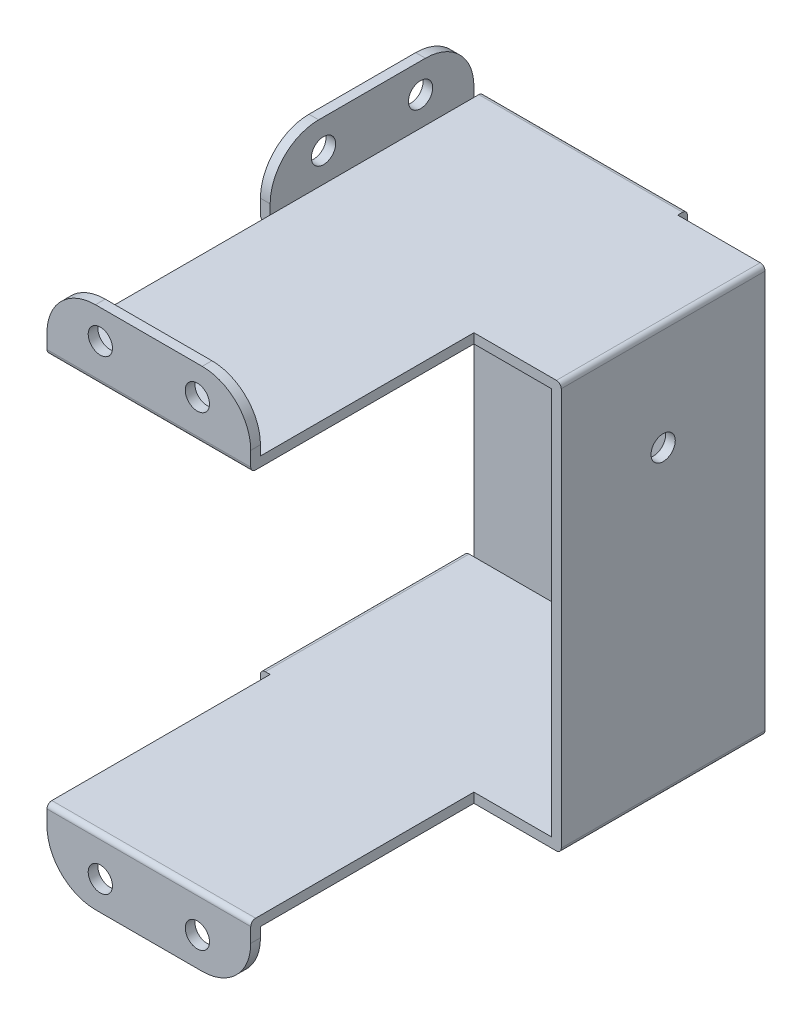
SolidWorks part; units mm, degrees
ref_plane "前视基准面" through (0, 0, 0) normal (0, 0, 1) x (1, 0, 0)
ref_plane "上视基准面" through (0, 0, 0) normal (0, 1, 0) x (1, 0, 0)
ref_plane "右视基准面" through (0, 0, 0) normal (1, 0, 0) x (0, 0, -1)
sketch "草图1" plane through (0, 0, 0) normal (0, 1, 0) x (1, 0, 0)
  line L0 (0, 0) -> (-31, 0)
  line L1 (-31, 0) -> (-31, 21)
  line L2 (-31, 21) -> (0, 21)
  line L3 (0, 21) -> (0, 0)
  dimension "D1" = 21
  dimension "D2" = 31
extrude "凸台-拉伸1" add sketch "草图1" along normal blind 42
shell "抽壳1" thickness 1 removed face at (-15.5, 21, -21) removed face at (-31, 21, -10.5) removed face at (-15.5, 21, 0)
sketch "草图2" plane through (0, 42, 0) normal (0, 1, 0) x (1, 0, 0)
  line L0 (-26, 21) -> (-26, 0)
  line L1 (0, 21) -> (-31, 21) construction
  line L2 (-31, 0) -> (0, 0) construction
  line L3 (-26, 0) -> (-31, 0)
  line L4 (-31, 0) -> (-31, 21)
  line L5 (-31, 21) -> (-26, 21)
  dimension "D1" = 5
extrude "凸台-拉伸2" add sketch "草图2" along normal blind 6
shell "抽壳2" thickness 1 removed face at (-17.8, 26.4, -21) removed face at (-17.8, 26.4, 0) removed face at (-26, 45, -10.5) removed face at (-28.5, 48, -10.5)
sketch "草图3" plane through (0, 0, 0) normal (0, -1, 0) x (1, 0, 0)
  line L0 (-31, 0) -> (-26, 0)
  line L1 (-31, 0) -> (0, 0) construction
  line L2 (-26, 0) -> (-26, -21)
  line L3 (0, -21) -> (-31, -21) construction
  line L4 (-26, -21) -> (-31, -21)
  line L5 (-31, -21) -> (-31, 0)
  dimension "D1" = 5
extrude "凸台-拉伸3" add sketch "草图3" along normal blind 6
shell "抽壳3" thickness 1 removed face at (-19.8333, 21, -21) removed face at (-28.5, -6, -10.5) removed face at (-26, -3, -10.5) removed face at (-19.8333, 21, 0)
sketch "草图4" plane through (0, 0, 0) normal (0, 0, 1) x (1, 0, 0)
  line L0 (-30, 42) -> (-30, 41)
  line L1 (-31, 41) -> (-1, 41) construction
  line L2 (-30, 41) -> (-9, 41)
  line L3 (-9, 41) -> (-9, 42)
  line L4 (-30, 42) -> (0, 42) construction
  line L5 (-9, 42) -> (-30, 42)
  line L6 (-30, 0) -> (-30, 1)
  line L7 (-31, 1) -> (-1, 1) construction
  line L8 (-30, 1) -> (-9, 1)
  line L9 (-9, 1) -> (-9, 0)
  line L10 (-30, 0) -> (0, 0) construction
  line L11 (-9, 0) -> (-30, 0)
  dimension "D1" = 21
  dimension "D2" = 21
extrude "凸台-拉伸4" add sketch "草图4" along normal blind 23
sketch "草图5" plane through (0, 42, 0) normal (0, 1, 0) x (1, 0, 0)
  line L0 (-30, -23) -> (-9, -23)
  line L1 (-9, -23) -> (-9, -18)
  line L2 (-9, -23) -> (-9, 0) construction
  line L3 (-9, -18) -> (-30, -18)
  line L4 (-30, -23) -> (-30, 0) construction
  line L5 (-30, -18) -> (-30, -23)
  dimension "D1" = 5
extrude "凸台-拉伸5" add sketch "草图5" along normal blind 6
shell "抽壳4" thickness 1 removed face at (-19.5, 45, 18) removed face at (-30, 43.6667, 13.6667) removed face at (-9, 43.6667, 13.6667) removed face at (-19.5, 48, 20.5)
sketch "草图6" plane through (0, 0, 0) normal (0, -1, 0) x (1, 0, 0)
  line L0 (-30, 23) -> (-9, 23)
  line L1 (-9, 23) -> (-9, 18)
  line L2 (-9, 23) -> (-9, 0) construction
  line L3 (-9, 18) -> (-30, 18)
  line L4 (-30, 23) -> (-30, 0) construction
  line L5 (-30, 18) -> (-30, 23)
  dimension "D1" = 5
extrude "凸台-拉伸6" add sketch "草图6" along normal blind 6
shell "抽壳5" thickness 1 removed face at (-30, -1.6667, 13.6667) removed face at (-19.5, -3, 18) removed face at (-19.5, -6, 20.5) removed face at (-9, -1.6667, 13.6667)
ref_plane "基准面1" through (-30, 42, -21) normal (-1, 0, 0) x (0, 0, 1)
sketch "草图8" plane through (0, 0, -21) normal (0, 0, -1) x (-1, 0, 0)
  line L0 (30, 42) -> (30, 0)
  line L1 (30, 39.525) -> (30, 44.475) construction
  line L2 (30, 42) -> (9, 42) construction
  line L3 (30, 0) -> (9, 0)
  line L4 (9, 0) -> (9, 42)
  line L5 (0, 42) -> (30, 42) construction
  line L6 (9, 42) -> (30, 42)
extrude "凸台-拉伸7" add sketch "草图8" along normal blind 1
hole_wizard "M3 螺纹孔1" positions "草图9" profile "草图11" tap size "M3" standard "GB" end condition up to next
sketch "草图9" plane through (0, 0, 23) normal (0, 0, 1) x (1, 0, 0)
  line L0 (-9, -6) -> (-30, -6) construction
  line L1 (-30, 48) -> (-9, 48) construction
  point P0 (-24.5, 45)
  point P2 (-14.5, 45)
  point P4 (-24.5, -3)
  point P6 (-14.5, -3)
  point P18 (-19.5, 48)
  dimension "D1" = 3
  dimension "D2" = 3
  dimension "D3" = 5
  dimension "D4" = 5
sketch "草图11" plane through (-24.5, 45, 23) normal (1, 0, 0) x (0, -1, 0)
  line L0 (0, 0) -> (0, 1)
  line L1 (0, 1) -> (1.25, 1)
  line L2 (1.25, 1) -> (1.25, 0)
  line L5 (1.25, 0) -> (0, 0)
  line L11 (0, -6.35) -> (0, 107.95) construction
  dimension "通孔螺纹孔钻头直径" = 2.5
  dimension "通孔螺纹孔钻头深度" = 1
cosmetic thread "孔螺蚊线1" parameters "D2"=3
cosmetic thread "孔螺蚊线2" parameters "D2"=3
cosmetic thread "孔螺蚊线3" parameters "D2"=3
cosmetic thread "孔螺蚊线4" parameters "D2"=3
hole_wizard "M3 螺纹孔2" positions "草图12" profile "草图13" tap size "M3" standard "GB" end condition up to next
sketch "草图12" plane through (-31, 0, 0) normal (-1, 0, 0) x (0, 0, 1)
  line L0 (-21, 48) -> (0, 48) construction
  line L1 (0, -6) -> (-21, -6) construction
  point P0 (-5.5, 45)
  point P2 (-15.5, 45)
  point P4 (-15.5, -3)
  point P6 (-5.5, -3)
  point P19 (-10.5, -6)
  point P20 (-10.5, 48)
  dimension "D1" = 3
  dimension "D2" = 3
  dimension "D3" = 5
  dimension "D4" = 5
  dimension "D5" = 5
sketch "草图13" plane through (-31, 45, -5.5) normal (0, 1, 0) x (0, 0, 1)
  line L0 (0, 0) -> (0, 1)
  line L1 (0, 1) -> (1.25, 1)
  line L2 (1.25, 1) -> (1.25, 0)
  line L5 (1.25, 0) -> (0, 0)
  line L11 (0, -6.35) -> (0, 107.95) construction
  dimension "通孔螺纹孔钻头直径" = 2.5
  dimension "通孔螺纹孔钻头深度" = 1
cosmetic thread "孔螺蚊线5" parameters "D2"=3
cosmetic thread "孔螺蚊线6" parameters "D2"=3
cosmetic thread "孔螺蚊线7" parameters "D2"=3
cosmetic thread "孔螺蚊线8" parameters "D2"=3
hole_wizard "M3 螺纹孔3" positions "草图14" profile "草图15" tap size "M3" standard "GB" end condition up to next
sketch "草图14" plane through (0, 0, 0) normal (1, 0, 0) x (0, 0, -1)
  line L0 (0, 42) -> (21, 42) construction
  line L1 (21, 42) -> (0, 42) construction
  point P0 (10.5, 31)
  point P7 (10.5, 42)
  dimension "D1" = 11
sketch "草图15" plane through (0, 31, -10.5) normal (0, 1, 0) x (0, 0, -1)
  line L0 (0, 0) -> (0, 1)
  line L1 (0, 1) -> (1.25, 1)
  line L2 (1.25, 1) -> (1.25, 0)
  line L5 (1.25, 0) -> (0, 0)
  line L11 (0, -6.35) -> (0, 107.95) construction
  dimension "通孔螺纹孔钻头直径" = 2.5
  dimension "通孔螺纹孔钻头深度" = 1
cosmetic thread "孔螺蚊线9" parameters "D2"=3
hole_wizard "M3 螺纹孔4" positions "草图16" profile "草图17" tap size "M3" standard "GB" end condition up to next
sketch "草图16" plane through (0, 0, -22) normal (0, 0, -1) x (-1, 0, 0)
  line L0 (30, 42) -> (9, 42) construction
  point P0 (19.5, 31)
  point P5 (19.5, 42)
  dimension "D1" = 11
sketch "草图17" plane through (-19.5, 31, -22) normal (1, 0, 0) x (0, 1, 0)
  line L0 (0, 0) -> (0, 1)
  line L1 (0, 1) -> (1.25, 1)
  line L2 (1.25, 1) -> (1.25, 0)
  line L5 (1.25, 0) -> (0, 0)
  line L11 (0, -6.35) -> (0, 107.95) construction
  dimension "通孔螺纹孔钻头直径" = 2.5
  dimension "通孔螺纹孔钻头深度" = 1
cosmetic thread "孔螺蚊线10" parameters "D2"=3
fillet "圆角2" radius 0.5 8 edges at (-31, 1, -10.5) (-31, 41, -10.5) (-19.5, 1, 23) (-19.5, 41, 23) (-19.5, 0, -22) (-19.5, 42, -22) (0, 0, -10.5) (0, 42, -10.5)
fillet "圆角3" radius 5 8 edges at (-30.5, -6, -21) (-30.5, -6, 0) (-30, -6, 22.5) (-9, -6, 22.5) (-9, 48, 22.5) (-30, 48, 22.5) (-30.5, 48, -21) (-30.5, 48, 0)
